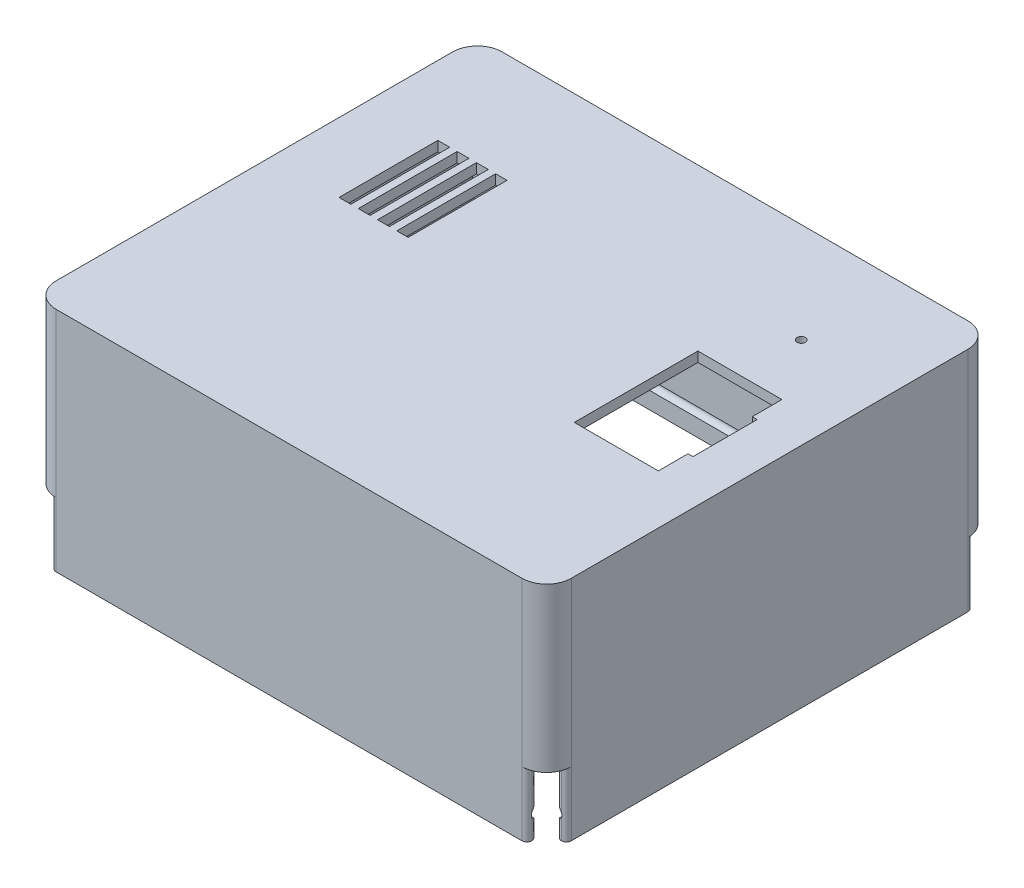
SolidWorks part; units mm, degrees
ref_plane "Plan de face" through (0, 0, 0) normal (0, 0, 1) x (1, 0, 0)
ref_plane "Plan de dessus" through (0, 0, 0) normal (0, 1, 0) x (1, 0, 0)
ref_plane "Plan de droite" through (0, 0, 0) normal (1, 0, 0) x (0, 0, -1)
sketch "Esquisse1" plane through (0, 0, 0) normal (0, 1, 0) x (1, 0, 0)
  line L1 (-52.1, -45.1) -> (52.1, -45.1)
  line L2 (-52.1, -45.1) -> (-52.1, 45.1)
  line L3 (-52.1, 45.1) -> (52.1, 45.1)
  line L4 (52.1, -45.1) -> (52.1, 45.1)
  line L5 (-52.1, -45.1) -> (52.1, 45.1) construction
  line L6 (-52.1, 45.1) -> (52.1, -45.1) construction
  point P0 (0, 0)
  dimension "D1" = 104.2
  dimension "D2" = 90.2
extrude "Boss.-Extru.1" add sketch "Esquisse1" along normal blind 2
sketch "Esquisse2" plane through (0, 0, 0) normal (0, -1, 0) x (1, 0, 0)
  line L8 (50.1, -43.1) -> (50.1, 43.1)
  line L9 (50.1, 43.1) -> (-50.1, 43.1)
  line L10 (-50.1, 43.1) -> (-50.1, -43.1)
  line L11 (-50.1, -43.1) -> (50.1, -43.1)
  line L12 (50.1, -43.1) -> (50.1, 43.1)
  line L13 (50.1, 43.1) -> (-50.1, 43.1)
  line L14 (-50.1, 43.1) -> (-50.1, -43.1)
  line L15 (-50.1, -43.1) -> (50.1, -43.1)
  line L16 (52.1, -45.1) -> (52.1, 45.1)
  line L17 (52.1, 45.1) -> (-52.1, 45.1)
  line L18 (-52.1, 45.1) -> (-52.1, -45.1)
  line L19 (-52.1, -45.1) -> (52.1, -45.1)
  line L20 (52.1, -45.1) -> (52.1, 45.1)
  line L21 (52.1, 45.1) -> (-52.1, 45.1)
  line L22 (-52.1, 45.1) -> (-52.1, -45.1)
  line L23 (-52.1, -45.1) -> (52.1, -45.1)
  dimension "D1" = 2
  dimension "D2" = 0
extrude "Boss.-Extru.2" add sketch "Esquisse2" along normal blind 44
sketch "Esquisse3" plane through (0, -44, 0) normal (0, -1, 0) x (1, 0, 0)
  line L0 (-50.1, 41.1) -> (-50.1, 43.1)
  line L1 (-52.1, 45.1) -> (-48.1, 45.1)
  line L2 (-52.1, 45.1) -> (-52.1, 41.1)
  line L3 (-52.1, 41.1) -> (-50.1, 41.1)
  line L4 (-48.1, 45.1) -> (-48.1, 43.1)
  line L5 (-50.1, 43.1) -> (-48.1, 43.1)
  dimension "D1" = 4
  dimension "D2" = 4
  dimension "D3" = 2
  dimension "D4" = 2
extrude "Enlèv. mat.-Extru.1" cut sketch "Esquisse3" against normal blind 13
mirror "Symétrie1" about plane through (0, 0, 0) normal (0, 0, 1) of "Enlèv. mat.-Extru.1"
mirror "Symétrie2" about plane through (0, 0, 0) normal (1, 0, 0) of "Symétrie1"
fillet "Congé3" radius 1 16 edges at (-48.1, -37.5, 45.1) (-48.1, -37.5, 43.1) (-50.1, -37.5, 41.1) (-52.1, -37.5, 41.1) (48.1, -37.5, 45.1) (48.1, -37.5, 43.1) (52.1, -37.5, 41.1) (50.1, -37.5, 41.1) (52.1, -37.5, -41.1) (50.1, -37.5, -41.1) (48.1, -37.5, -43.1) (48.1, -37.5, -45.1) (-48.1, -37.5, -45.1) (-48.1, -37.5, -43.1) (-50.1, -37.5, -41.1) (-52.1, -37.5, -41.1)
fillet "Congé1" radius 5 4 edges at (52.1, -14.5, 45.1) (52.1, -14.5, -45.1) (-52.1, -14.5, -45.1) (-52.1, -14.5, 45.1)
sketch "Esquisse4" plane through (0, 0, 0) normal (1, 0, 0) x (0, 0, -1)
  line L0 (-43.1, -31) -> (-43.1, -44) construction
  line L1 (-43.1, -38.4) -> (-43.1, -40.6)
  line L2 (-44.1, -44) -> (-43.1, -44) construction
  arc A1 (-43.1, -38.4) -> (-43.1, -40.6) centre (-43.1, -39.5) ccw
  dimension "D1" = 1.1
  dimension "D2" = 4.5
extrude "Enlèv. mat.-Extru.2" cut sketch "Esquisse4" against normal through all both and the other way through all
mirror "Symétrie4" about plane through (0, 0, 0) normal (0, 0, 1) of "Enlèv. mat.-Extru.2"
sketch "Esquisse5" plane through (0, 0, 0) normal (0, 0, 1) x (1, 0, 0)
  line L0 (-50.1, -31) -> (-50.1, -44) construction
  line L1 (-51.1, -44) -> (-50.1, -44) construction
  line L2 (-50.1, -38.4) -> (-50.1, -40.6)
  arc A0 (-50.1, -38.4) -> (-50.1, -40.6) centre (-50.1, -39.5) ccw
  dimension "D1" = 1.1
  dimension "D2" = 4.5
extrude "Enlèv. mat.-Extru.3" cut sketch "Esquisse5" against normal through all both and the other way through all
mirror "Symétrie5" about plane through (0, 0, 0) normal (1, 0, 0) of "Enlèv. mat.-Extru.3"
sketch "Esquisse6" [suppressed] plane through (-52.1, 0, 0) normal (-1, 0, 0) x (0, 0, 1)
  line L0 (0, 15.9382) -> (0, -19.3286) construction
  line L1 (-40.1, 2) -> (40.1, 2) construction
  line L2 (-10.15, -14) -> (10.15, -14)
  line L3 (-10.15, -14) -> (-10.15, 0)
  line L4 (-10.15, 0) -> (10.15, 0)
  line L5 (10.15, -14) -> (10.15, 0)
  line L6 (-10.15, -14) -> (10.15, 0) construction
  line L7 (-10.15, 0) -> (10.15, -14) construction
  point P3 (0, -7)
  dimension "D1" = 14
  dimension "D2" = 2
  dimension "D3" = 20.3
extrude "Enlèv. mat.-Extru.4" [suppressed] cut sketch "Esquisse6" against normal blind 5 and the other way through all
sketch "Esquisse7" plane through (-52.1, 0, 0) normal (-1, 0, 0) x (0, 0, 1)
  line L0 (0, 0) -> (0, 2) construction
  line L1 (-40.1, 2) -> (40.1, 2) construction
  line L3 (-8.1, 0) -> (8.1, 0)
  line L4 (-8.1, 0) -> (-8.1, 2)
  line L5 (-8.1, 2) -> (8.1, 2)
  line L6 (8.1, 0) -> (8.1, 2)
  line L7 (-8.1, 0) -> (8.1, 2) construction
  line L8 (-8.1, 2) -> (8.1, 0) construction
  point P7 (0, 1)
  dimension "D1" = 16.2
extrude "Enlèv. mat.-Extru.5" [suppressed] cut sketch "Esquisse7" against normal blind 18.3
sketch "Esquisse8" plane through (0, 2, 0) normal (0, 1, 0) x (1, 0, 0)
  line L0 (0, 0) -> (52.1, 0) construction
  line L1 (52.1, -40.1) -> (52.1, 40.1) construction
  line L3 (9.8, -18.8) -> (42.1, -18.8)
  line L4 (9.8, -18.8) -> (9.8, 18.8)
  line L5 (9.8, 18.8) -> (42.1, 18.8)
  line L6 (42.1, -18.8) -> (42.1, 18.8)
  line L7 (9.8, -18.8) -> (42.1, 18.8) construction
  line L8 (9.8, 18.8) -> (42.1, -18.8) construction
  point P5 (25.95, 0)
  dimension "D1" = 32.3
  dimension "D2" = 37.6
  dimension "D3" = 10
extrude "Enlèv. mat.-Extru.6" [suppressed] cut sketch "Esquisse8" against normal blind 3
sketch "Esquisse9" [suppressed] plane through (0, 0, 0) normal (0, -1, 0) x (1, 0, 0)
  line L0 (9.8, 18.8) -> (9.8, -18.8) construction
  line L1 (3.8, -24.8) -> (48.1, -24.8)
  line L2 (3.8, -24.8) -> (3.8, 24.8)
  line L3 (3.8, 24.8) -> (48.1, 24.8)
  line L4 (48.1, -24.8) -> (48.1, 24.8)
  line L5 (3.8, -24.8) -> (48.1, 24.8) construction
  line L6 (3.8, 24.8) -> (48.1, -24.8) construction
  line L7 (42.1, 18.8) -> (9.8, 18.8) construction
  line L8 (42.1, -18.8) -> (42.1, 18.8) construction
  line L9 (9.8, -18.8) -> (42.1, -18.8) construction
  line L10 (42.1, 18.8) -> (9.8, 18.8)
  line L11 (42.1, -18.8) -> (42.1, 18.8)
  line L12 (9.8, -18.8) -> (42.1, -18.8)
  line L13 (9.8, 18.8) -> (9.8, -18.8)
  point P0 (25.95, 0)
  dimension "D1" = 6
  dimension "D2" = 6
  dimension "D3" = 6
  dimension "D4" = 6
extrude "Boss.-Extru.3" [suppressed] add sketch "Esquisse9" along normal blind 2
sketch "Esquisse10" [suppressed] plane through (0, 2, 0) normal (0, 1, 0) x (1, 0, 0)
  line L0 (25.95, 18.8) -> (25.95, -18.8) construction
  line L1 (42.1, 18.8) -> (9.8, 18.8) construction
  line L2 (9.8, -18.8) -> (42.1, -18.8) construction
  line L4 (17.95, -18.8) -> (33.95, -18.8)
  line L5 (17.95, -18.8) -> (17.95, -20.8)
  line L6 (17.95, -20.8) -> (33.95, -20.8)
  line L7 (33.95, -18.8) -> (33.95, -20.8)
  dimension "D1" = 2
  dimension "D2" = 16
sketch "Esquisse11" [suppressed] plane through (0, 0, 0) normal (0, 1, 0) x (1, 0, 0)
  line L0 (-52.1, 0) -> (-32.1, 0) construction
  line L1 (-52.1, 10.15) -> (-52.1, -10.15) construction
  line L3 (-52.1, 40.1) -> (-52.1, 8.1) construction
  line L4 (-52.1, -10.15) -> (-32.1, -10.15)
  line L5 (-52.1, -10.15) -> (-52.1, 10.15)
  line L6 (-52.1, 10.15) -> (-32.1, 10.15)
  line L7 (-32.1, -10.15) -> (-32.1, 10.15)
  line L8 (-52.1, -10.15) -> (-32.1, 10.15) construction
  line L9 (-52.1, 10.15) -> (-32.1, -10.15) construction
  point P6 (-42.1, 0)
  dimension "D1" = 20.3
  dimension "D2" = 20
extrude "Enlèv. mat.-Extru.8" [suppressed] cut sketch "Esquisse11" along normal blind 0.4
sketch "Esquisse13" [suppressed] plane through (0, -2, 0) normal (0, -1, 0) x (1, 0, 0)
  line L0 (42.1, -18.8) -> (42.1, 18.8) construction
  line L1 (9.8, 18.8) -> (9.8, -18.8) construction
  line L2 (9.8, -18.8) -> (42.1, -18.8) construction
  circle A0 centre (45.3, -10.8) radius 0.75
  circle A1 centre (5.2, 9.2) radius 0.75
  circle A2 centre (15.6, -21.4) radius 0.75
  dimension "D5" = 1.5
  dimension "D6" = 1.5
  dimension "D9" = 1.5
  dimension "D1" = 3.2
  dimension "D2" = 4.6
  dimension "D3" = 8
  dimension "D4" = 28
  dimension "D7" = 2.6
  dimension "D8" = 5.8
extrude "Enlèv. mat.-Extru.9" [suppressed] cut sketch "Esquisse13" against normal blind 3
sketch "Esquisse14" [suppressed] plane through (0, -2, 0) normal (0, -1, 0) x (1, 0, 0)
  line L0 (3.8, 11.3909) -> (3.8, 7.0091)
  line L1 (3.8, 24.8) -> (3.8, -24.8) construction
  line L2 (3.8, 24.8) -> (3.8, -24.8) construction
  arc A0 (3.8, 11.3909) -> (3.8, 7.0091) centre (5.2, 9.2) ccw
  dimension "D1" = 5.2
extrude "Boss.-Extru.4" [suppressed] add sketch "Esquisse14" against normal up to surface (2 mm away)
sketch "Esquisse15" plane through (0, -44, 0) normal (0, -1, 0) x (1, 0, 0)
  line L0 (-50.1, 40.1) -> (-50.1, -40.1) construction
  line L1 (50.3, -43.3) -> (-50.3, -43.3)
  line L2 (50.3, -43.3) -> (50.3, 43.3)
  line L3 (50.3, 43.3) -> (-50.3, 43.3)
  line L4 (-50.3, -43.3) -> (-50.3, 43.3)
  line L5 (50.3, -43.3) -> (-50.3, 43.3) construction
  line L6 (50.3, 43.3) -> (-50.3, -43.3) construction
  line L7 (47.1, 43.1) -> (-47.1, 43.1) construction
  point P0 (0, 0)
  dimension "D1" = 0.2
  dimension "D2" = 0.2
extrude "Enlèv. mat.-Extru.10" cut sketch "Esquisse15" against normal blind 4.5
sketch "Esquisse16" plane through (-52.1, 0, 0) normal (-1, 0, 0) x (0, 0, 1)
  circle A0 centre (-13, -7) radius 1.5
  dimension "D1" = 3
extrude "Enlèv. mat.-Extru.11" [suppressed] cut sketch "Esquisse16" against normal blind 4
mirror "Symétrie6" [suppressed] about plane through (0, 0, 0) normal (0, 0, 1)
sketch "Esquisse17" plane through (0, 0, 0) normal (0, -1, 0) x (1, 0, 0)
  line L0 (-50.1, 0) -> (0, 0) construction
  line L1 (-50.1, 43.1) -> (-50.1, -43.1) construction
  line L2 (-50.1, 40.1) -> (-50.1, 43.1) construction
  line L3 (-38.1, -23.1) -> (-24.1, -23.1)
  line L4 (-38.1, -23.1) -> (-38.1, -3.1)
  line L5 (-38.1, -3.1) -> (-24.1, -3.1)
  line L6 (-24.1, -23.1) -> (-24.1, -3.1)
  line L7 (-38.1, -23.1) -> (-24.1, -3.1) construction
  line L8 (-38.1, -3.1) -> (-24.1, -23.1) construction
  line L9 (-50.1, -43.1) -> (50.1, -43.1) construction
  point P5 (-31.1, -13.1)
  dimension "D1" = 14
  dimension "D2" = 20
  dimension "D3" = 12
  dimension "D4" = 20
extrude "Enlèv. mat.-Extru.12" cut sketch "Esquisse17" against normal up to next
sketch "Esquisse19" plane through (0, 0, 0) normal (0, -1, 0) x (1, 0, 0)
  line L6 (-38.1, -23.1) -> (-24.1, -23.1) construction
  line L7 (-41.1, 2.4) -> (-21.1, 2.4) construction
  line L8 (-41.1, 2.4) -> (-41.1, -28.1) construction
  line L9 (-41.1, -28.1) -> (-21.1, -28.1) construction
  line L10 (-21.1, 2.4) -> (-21.1, -28.1) construction
  line L12 (-38.1, -3.1) -> (-38.1, -23.1) construction
  circle A0 centre (-41.1, 1.9) radius 3.5
  circle A1 centre (-31.1, -28.1) radius 3.5
  circle A2 centre (-21.1, 1.9) radius 3.5
  dimension "D5" = 7
  dimension "D6" = 7
  dimension "D7" = 7
  dimension "D1" = 20
  dimension "D2" = 30.5
  dimension "D13" = 10
  dimension "D3" = 5
  dimension "D4" = 7
  dimension "D8" = 30
extrude "Boss.-Extru.5" add sketch "Esquisse19" along normal blind 6
sketch "Esquisse20" plane through (0, -6, 0) normal (0, -1, 0) x (1, 0, 0)
  circle A0 centre (-41.1, 1.9) radius 0.85
  circle A1 centre (-21.1, 1.9) radius 0.85
  circle A3 centre (-31.1, -28.1) radius 0.85
  dimension "D1" = 1.7
  dimension "D3" = 1.7
  dimension "D5" = 1.7
extrude "Enlèv. mat.-Extru.13" cut sketch "Esquisse20" against normal blind 6.5
sketch "Esquisse21" plane through (0, 2, 0) normal (0, 1, 0) x (1, 0, 0)
  line L1 (-50.0193, 44.4136) -> (-2.2418, 44.4136)
  line L2 (-50.0193, 44.4136) -> (-50.0193, -40.4592)
  line L3 (-50.0193, -40.4592) -> (-2.2418, -40.4592)
  line L4 (-2.2418, 44.4136) -> (-2.2418, -40.4592)
  line L5 (-61.088, 55.0958) -> (60.8078, 55.0958)
  line L6 (-61.088, 55.0958) -> (-61.088, -50.267)
  line L7 (-61.088, -50.267) -> (60.8078, -50.267)
  line L8 (60.8078, 55.0958) -> (60.8078, -50.267)
extrude "Enlèv. mat.-Extru.14" [suppressed] cut sketch "Esquisse21" against normal through all
sketch "Esquisse22" [suppressed] plane through (0, 0, -44.4136) normal (0, 0, -1) x (-1, 0, 0)
  line L1 (-3.5624, -9.8336) -> (56.1199, -9.8336)
  line L2 (-3.5624, -9.8336) -> (-3.5624, -57.8347)
  line L3 (-3.5624, -57.8347) -> (56.1199, -57.8347)
  line L4 (56.1199, -9.8336) -> (56.1199, -57.8347)
extrude "Enlèv. mat.-Extru.15" [suppressed] cut sketch "Esquisse22" against normal through all
sketch "Esquisse23" plane through (0, 2, 0) normal (0, 1, 0) x (1, 0, 0)
  line L0 (52.1, -40.1) -> (52.1, 40.1) construction
  line L1 (25.1, -12.5) -> (42.1, -12.5)
  line L2 (25.1, -12.5) -> (25.1, 12.5)
  line L3 (25.1, 12.5) -> (42.1, 12.5)
  line L4 (42.1, -12.5) -> (42.1, 12.5)
  line L5 (25.1, -12.5) -> (42.1, 12.5) construction
  line L6 (25.1, 12.5) -> (42.1, -12.5) construction
  line L7 (52.1, 0) -> (11.5296, 0) construction
  point P0 (33.6, 0)
  dimension "D1" = 17
  dimension "D2" = 25
  dimension "D3" = 10
extrude "Enlèv. mat.-Extru.16" cut sketch "Esquisse23" against normal up to next
sketch "Esquisse24" plane through (0, 0, 0) normal (0, -1, 0) x (1, 0, 0)
  line L0 (33.6, -12.5) -> (33.6, -24.9) construction
  line L1 (42.1, -12.5) -> (25.1, -12.5) construction
  circle A0 centre (33.6, -24.9) radius 0.85
  dimension "D2" = 1.7
  dimension "D1" = 12.4
extrude "Enlèv. mat.-Extru.17" cut sketch "Esquisse24" against normal up to next
sketch "Esquisse25" plane through (0, 2, 0) normal (0, 1, 0) x (1, 0, 0)
  line L0 (52.1, 0) -> (32.4174, 0) construction
  line L1 (52.1, -40.1) -> (52.1, 40.1) construction
  line L2 (42.1, -12.5) -> (42.1, 12.5) construction
  line L3 (42.1, -6.5) -> (43.1, -6.5)
  line L4 (42.1, -6.5) -> (42.1, 6.5)
  line L5 (42.1, 6.5) -> (43.1, 6.5)
  line L6 (43.1, -6.5) -> (43.1, 6.5)
  line L7 (42.1, -6.5) -> (43.1, 6.5) construction
  line L8 (42.1, 6.5) -> (43.1, -6.5) construction
  point P5 (42.6, 0)
  dimension "D1" = 1
  dimension "D2" = 13
extrude "Enlèv. mat.-Extru.18" cut sketch "Esquisse25" against normal up to next
sketch "Esquisse26" plane through (0, 0, 0) normal (0, -1, 0) x (1, 0, 0)
  line L0 (33.6, 12.5) -> (33.6, 21.3805) construction
  line L1 (25.1, 12.5) -> (42.1, 12.5) construction
  line L3 (21.6, 18) -> (45.6, 18)
  line L4 (21.6, 18) -> (21.6, 16)
  line L5 (21.6, 16) -> (45.6, 16)
  line L6 (45.6, 18) -> (45.6, 16)
  line L7 (21.6, 18) -> (45.6, 16) construction
  line L8 (21.6, 16) -> (45.6, 18) construction
  line L9 (21.6, 16) -> (23.4, 16)
  line L10 (21.6, 16) -> (21.6, 10.5)
  line L11 (21.6, 10.5) -> (23.4, 10.5)
  line L12 (23.4, 16) -> (23.4, 10.5)
  line L13 (45.6, 16) -> (44.6, 16)
  line L14 (45.6, 16) -> (45.6, 10.5)
  line L15 (45.6, 10.5) -> (44.6, 10.5)
  line L16 (44.6, 16) -> (44.6, 10.5)
  point P4 (33.6, 17)
  point P15 (45.1, 10.5)
  dimension "D1" = 24
  dimension "D2" = 2
  dimension "D3" = 3.5
  dimension "D4" = 21.2
  dimension "D5" = 11
  dimension "D6" = 2
extrude "Boss.-Extru.6" add sketch "Esquisse26" along normal blind 2.1 contours L12 L5 L10 L11 | L6 L3 L4 L5 | L5 L16 L15 L14 region at (33.6, 0, 17) region at (22.5, 0, 13.25) region at (45.1, 0, 13.25)
sketch "Esquisse27" plane through (0, -2.1, 0) normal (0, -1, 0) x (1, 0, 0)
  line L0 (33.6, 18) -> (33.6, 8.4026) construction
  line L1 (21.6, 18) -> (27.1, 18)
  line L2 (21.6, 18) -> (21.6, 10.5)
  line L3 (21.6, 10.5) -> (27.1, 10.5)
  line L4 (27.1, 18) -> (27.1, 10.5)
  line L5 (45.6, 18) -> (40.1, 18)
  line L6 (45.6, 18) -> (45.6, 10.5)
  line L7 (45.6, 10.5) -> (40.1, 10.5)
  line L8 (40.1, 18) -> (40.1, 10.5)
  line L9 (21.6, 18) -> (45.6, 18) construction
  line L10 (25.1, 12.5) -> (42.1, 12.5) construction
  dimension "D1" = 13
  dimension "D2" = 2
extrude "Boss.-Extru.7" add sketch "Esquisse27" along normal blind 2
sketch "Esquisse28" plane through (0, -44, 0) normal (0, -1, 0) x (1, 0, 0)
  line L1 (-74.2005, 67.4898) -> (79.4276, 67.4898)
  line L2 (-74.2005, 67.4898) -> (-74.2005, -77.2581)
  line L3 (-74.2005, -77.2581) -> (79.4276, -77.2581)
  line L4 (79.4276, 67.4898) -> (79.4276, -77.2581)
  line L5 (-47.1432, 7.6085) -> (-7.5923, 7.6085)
  line L6 (-47.1432, 7.6085) -> (-47.1432, -39.9584)
  line L7 (-47.1432, -39.9584) -> (-7.5923, -39.9584)
  line L8 (-7.5923, 7.6085) -> (-7.5923, -39.9584)
extrude "Enlèv. mat.-Extru.19" [suppressed] cut sketch "Esquisse28" against normal through all
sketch "Esquisse29" plane through (0, 0, 0) normal (0, -1, 0) x (1, 0, 0)
  line L0 (-24.1, -3.1) -> (-38.1, -3.1) construction
  line L1 (-35.7, -3.1) -> (-34.2, -3.1)
  line L2 (-35.7, -3.1) -> (-35.7, -23.1)
  line L3 (-35.7, -23.1) -> (-34.2, -23.1)
  line L4 (-34.2, -3.1) -> (-34.2, -23.1)
  line L5 (-38.1, -23.1) -> (-24.1, -23.1) construction
  line L6 (-38.1, -3.1) -> (-38.1, -23.1) construction
  dimension "D1" = 2.4
  dimension "D2" = 1.5
extrude "Boss.-Extru.8" add sketch "Esquisse29" against normal up to surface (2 mm away) up to face at (33.6, 2, -25.75)
pattern_linear "Répétition linéaire1" count 3 spacing 3.9 along (1, 0, 0) of "Boss.-Extru.8"
fillet "Congé4" radius 3 4 edges at (-50.1, -15.5, -43.1) (50.1, -15.5, -43.1) (50.1, -15.5, 43.1) (-50.1, -15.5, 43.1)
equation "\"D6@Esquisse19\"=\"D5@Esquisse19\""
equation "\"D7@Esquisse19\"=\"D5@Esquisse19\""
equation "\"D3@Esquisse20\"=\"D1@Esquisse20\""
equation "\"D5@Esquisse20\"=\"D1@Esquisse20\""
